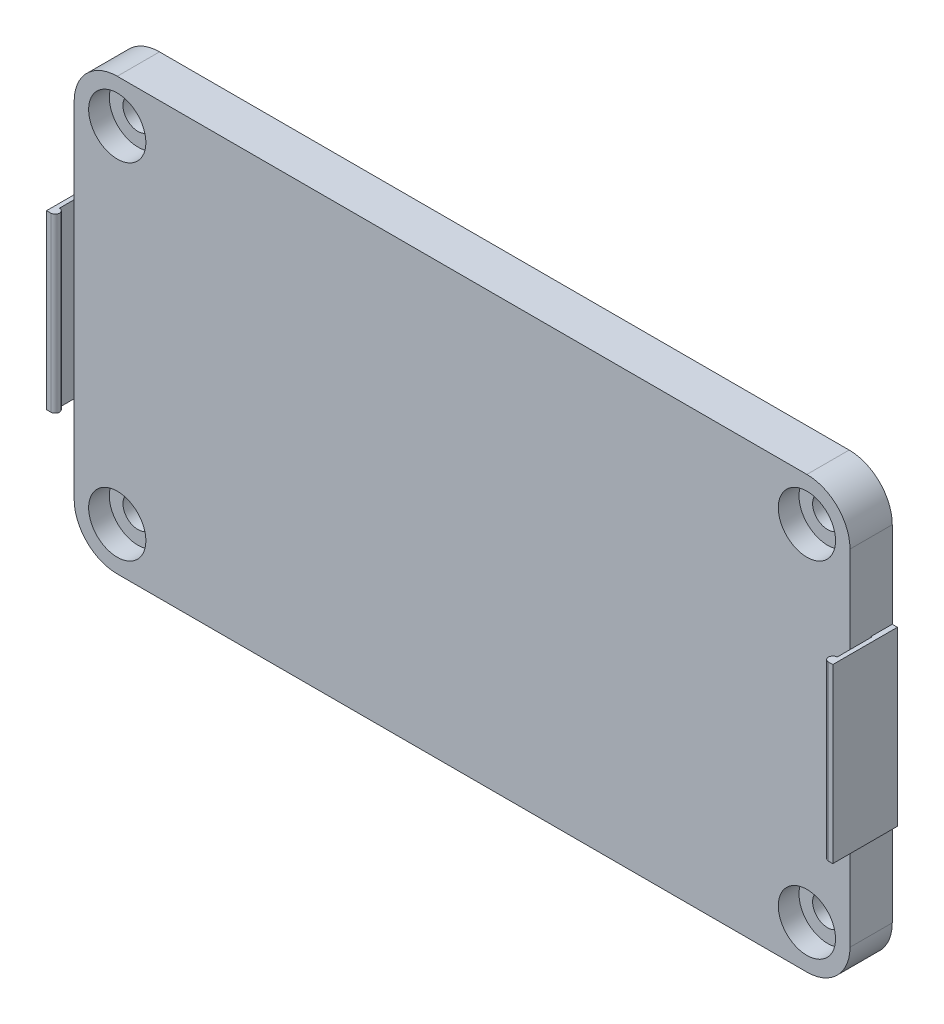
SolidWorks part; units mm, degrees
material "ABS"
ref_plane "Front Plane" through (0, 0, 0) normal (0, 0, 1) x (1, 0, 0)
ref_plane "Top Plane" through (0, 0, 0) normal (0, 1, 0) x (1, 0, 0)
ref_plane "Right Plane" through (0, 0, 0) normal (1, 0, 0) x (0, 0, -1)
sketch "Sketch1" plane through (0, 0, 0) normal (0, 0, 1) x (1, 0, 0)
  line L1 (-50.8, -31.75) -> (50.8, -31.75)
  line L2 (-57.15, -25.4) -> (-57.15, 25.4)
  line L3 (-50.8, 31.75) -> (50.8, 31.75)
  line L4 (57.15, -25.4) -> (57.15, 25.4)
  line L5 (-57.15, -31.75) -> (57.15, 31.75) construction
  line L6 (-57.15, 31.75) -> (57.15, -31.75) construction
  arc A0 (50.8, -31.75) -> (57.15, -25.4) centre (50.8, -25.4) ccw
  arc A1 (50.8, 31.75) -> (57.15, 25.4) centre (50.8, 25.4) cw
  arc A2 (-57.15, 25.4) -> (-50.8, 31.75) centre (-50.8, 25.4) cw
  arc A3 (-50.8, -31.75) -> (-57.15, -25.4) centre (-50.8, -25.4) cw
  circle A4 centre (-50.8, -25.4) radius 2.2098
  circle A5 centre (-50.8, 25.4) radius 2.2098
  circle A6 centre (50.8, 25.4) radius 2.2098
  circle A7 centre (50.8, -25.4) radius 2.2098
  point P0 (0, 0)
  dimension "D3" = 6.35
  dimension "D4" = 4.4196
  dimension "D1" = 114.3
  dimension "D2" = 63.5
extrude "Boss-Extrude1" add sketch "Sketch1" along normal blind 6.223
sketch "Sketch2" plane through (0, 0, 6.223) normal (0, 0, 1) x (1, 0, 0)
  circle A0 centre (-50.8, 25.4) radius 4.2164
  circle A1 centre (50.8, 25.4) radius 4.2164
  circle A2 centre (50.8, -25.4) radius 4.2164
  circle A3 centre (-50.8, -25.4) radius 4.2164
  dimension "D1" = 8.4328
extrude "Cut-Extrude1" cut sketch "Sketch2" against normal blind 3.048
sketch "Sketch4" plane through (0, 0, 0) normal (0, 0, 1) x (1, 0, 0)
  line L0 (-57.15, 25.4) -> (-57.15, -25.4) construction
  line L1 (-57.15, 12.7) -> (-57.912, 12.7)
  line L2 (-57.15, 12.7) -> (-57.15, -12.7)
  line L3 (-57.15, -12.7) -> (-57.912, -12.7)
  line L4 (-57.912, 12.7) -> (-57.912, -12.7)
  line L5 (0, -3.4226) -> (0, 3.4226) construction
  line L6 (57.15, -12.7) -> (57.912, -12.7)
  line L7 (57.912, 12.7) -> (57.912, -12.7)
  line L8 (57.15, 12.7) -> (57.912, 12.7)
  line L9 (57.15, 12.7) -> (57.15, -12.7)
  point P6 (-57.15, 0)
  dimension "D1" = 25.4
  dimension "D2" = 0.762
extrude "Boss-Extrude2" add sketch "Sketch4" along normal blind 3.1115
sketch "Sketch5" plane through (0, -12.7, 0) normal (0, -1, 0) x (1, 0, 0)
  line L0 (-57.277, 3.1115) -> (-57.912, 3.1115)
  line L2 (-57.912, 3.1115) -> (-57.912, 9.525)
  line L3 (-57.912, 9.525) -> (-57.277, 9.525)
  line L6 (-57.277, 8.255) -> (-57.277, 3.1115)
  line L12 (-57.912, 3.1115) -> (-57.15, 3.1115) construction
  line L13 (-57.912, 3.1115) -> (-57.912, 0) construction
  line L14 (0, -3.4226) -> (0, 3.4226) construction
  line L15 (57.912, 9.525) -> (57.277, 9.525)
  line L16 (57.912, 3.1115) -> (57.912, 9.525)
  line L17 (57.277, 3.1115) -> (57.912, 3.1115)
  line L18 (57.277, 8.255) -> (57.277, 3.1115)
  arc A0 (-57.277, 9.525) -> (-57.277, 8.255) centre (-57.277, 8.89) cw
  arc A2 (57.277, 9.525) -> (57.277, 8.255) centre (57.277, 8.89) ccw
  point P18 (-56.642, 8.89)
  dimension "D2" = 0.635
  dimension "D1" = 0.635
  dimension "D3" = 5.7785
extrude "Boss-Extrude3" add sketch "Sketch5" against normal up to surface (25.4 mm away) up to face at (-57.531, 12.7, 1.5557)
equation "\"wall-thickness\"= .2"
equation "\"tolerance\"= 0.005"
equation "\"D1@Boss-Extrude1\"= .115 + .125 + \"tolerance\""
equation "\"D4@Sketch1\"=.164 + \"tolerance\" * 2"
equation "\"D1@Sketch2\"= .322 + \"tolerance\" * 2"
equation "\"D1@Cut-Extrude1\"= .115 + \"tolerance\""
equation "\"D2@Sketch4\"=.025 + \"tolerance\""
equation "\"D3@Sketch5\"=(.125+0.08+\"tolerance\")/2+\"D1@Boss-Extrude2\""
equation "\"D1@Boss-Extrude2\"= \"D1@Boss-Extrude1\" / 2"
